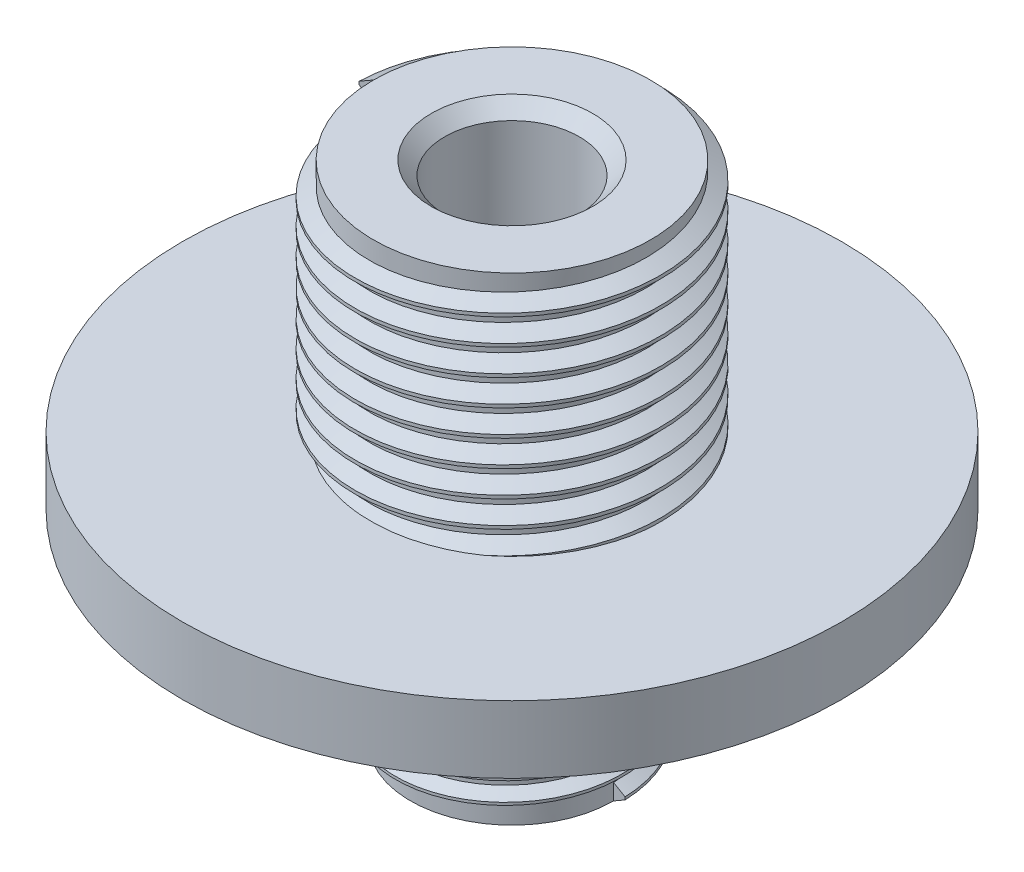
SolidWorks part; units mm, degrees
material "7075-T6 (SN)"
ref_plane "Ön Düzlem" through (0, 0, 0) normal (0, 0, 1) x (1, 0, 0)
ref_plane "Üst Düzlem" through (0, 0, 0) normal (0, 1, 0) x (1, 0, 0)
ref_plane "Sağ Düzlem" through (0, 0, 0) normal (1, 0, 0) x (0, 0, -1)
sketch "Sketch1" plane through (0, 0, 0) normal (0, 0, 1) x (1, 0, 0)
  line L0 (0, 26.5651) -> (0, -27.5918)
  line L3 (0, -17.5) -> (7.55, -17.5)
  line L5 (10.3, 20) -> (10.3, 2.5)
  line L6 (0, 20) -> (10.3, 20)
  line L7 (24.5, -2.5) -> (17, -2.5)
  line L8 (24.5, -2.5) -> (24.5, 2.5)
  line L9 (24.5, 2.5) -> (10.3, 2.5)
  line L13 (17, -7.5) -> (7.55, -7.5)
  line L19 (10.3, 26.5651) -> (10.3, -27.5918) construction
  line L20 (17, -7.5) -> (17, -2.5)
  line L21 (7.55, -7.5) -> (7.55, -17.5)
  point P0 (0, 0)
  point P5 (0, 0)
  point P11 (0, -5)
  dimension "D1" = 17.5
  dimension "D2" = 10.3
  dimension "D5" = 15
revolve "Revolve1" add sketch "Sketch1" angle 360 about L0
sketch "Sketch9" plane through (0, -7.5, 0) normal (0, -1, 0) x (1, 0, 0)
  line L7 (-0.3983, -13.8507) -> (11.7959, -7.2702)
  line L8 (11.7959, -7.2702) -> (12.1942, 6.5804)
  line L9 (12.1942, 6.5804) -> (0.3983, 13.8507)
  line L10 (0.3983, 13.8507) -> (-11.7959, 7.2702)
  line L11 (-11.7959, 7.2702) -> (-12.1942, -6.5804)
  line L12 (-12.1942, -6.5804) -> (-0.3983, -13.8507)
  circle A0 centre (0, 0) radius 17.5
  circle A2 centre (0, 0) radius 12 construction
  circle A3 centre (0, 0) radius 12 construction
thread "Thread1" pitch 1.9538 method extrude profile "Thread Profile2" start angle 0, offset 0, length 0, pitch 1.9538, diameter 20.6
ref_plane "Plane2" through (-10.3, 20, 0) normal (0, 0, 1) x (-1, 0, 0)
sketch "Thread Profile2" plane through (-10.3, 20, 0) normal (0, 0, 1) x (-1, 0, 0)
  line L0 (0, 0) -> (0, 1.9538) construction
  line L1 (0, 0) -> (1.0576, 0.6106)
  line L2 (1.0576, 0.6106) -> (1.0576, 0.8548)
  line L3 (1.0576, 0.8548) -> (0, 1.4654)
  line L4 (1.0576, 0.7327) -> (0, 0.7327) construction
  line L11 (0, 0) -> (0, 1.4654)
  point P2 (0, 0)
  dimension "Pitch" = 1.9538
  dimension "Profile_Angle" = 60
  dimension "Profile_Land" = 0.2442
  dimension "Profile_Height" = 1.0576
thread "Thread2" pitch 1.5875 method extrude profile "Thread Profile3" start angle 0, offset 0, length 0, pitch 1.5875, diameter 15.1
ref_plane "Plane3" through (7.55, -17.5, 0) normal (0, 0, 1) x (1, 0, 0)
sketch "Thread Profile3" plane through (7.55, -17.5, 0) normal (0, 0, 1) x (1, 0, 0)
  line L0 (0, 0) -> (0, 1.5875) construction
  line L1 (0, 0) -> (0.8593, 0.4961)
  line L2 (0.8593, 0.4961) -> (0.8593, 0.6945)
  line L3 (0.8593, 0.6945) -> (0, 1.1906)
  line L4 (0.8593, 0.5953) -> (0, 0.5953) construction
  line L11 (0, 0) -> (0, 1.1906)
  point P2 (0, 0)
  dimension "Pitch" = 1.5875
  dimension "Profile_Angle" = 60
  dimension "Profile_Land" = 0.1984
  dimension "Profile_Height" = 0.8593
sketch "Sketch26" plane through (0, 20, 0) normal (0, 1, 0) x (1, 0, 0)
  circle A0 centre (0, 0) radius 5
  dimension "D1" = 10
extrude "Cut-Extrude3" cut sketch "Sketch26" against normal blind 39
chamfer "Chamfer2" distance 1 angle 45 2 edges at (0, -17.5, 5) (0, 20, 5)
extrude "Cut-Extrude4" cut sketch "Sketch9" against normal blind 5
